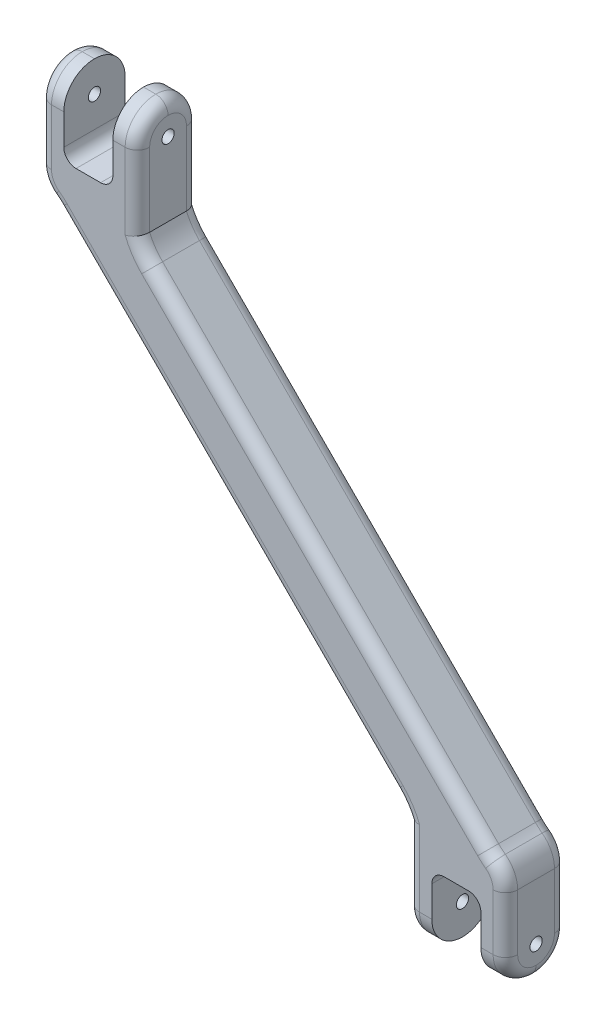
SolidWorks part; units mm, degrees
material "ABS"
ref_plane "Front Plane" through (0, 0, 0) normal (0, 0, 1) x (1, 0, 0)
ref_plane "Top Plane" through (0, 0, 0) normal (0, 1, 0) x (1, 0, 0)
ref_plane "Right Plane" through (0, 0, 0) normal (1, 0, 0) x (0, 0, -1)
sketch "Sketch1" plane through (0, 0, 0) normal (0, 0, 1) x (1, 0, 0)
  line L0 (-30, 30) -> (0, 0) construction
  line L1 (-38, 47) -> (-22, 47)
  line L2 (-38, 47) -> (-38, 30)
  line L3 (-38, 30) -> (-22, 30)
  line L4 (-22, 47) -> (-22, 30)
  line L5 (-34, 47) -> (-26, 47)
  line L6 (-34, 47) -> (-34, 35)
  line L7 (-34, 35) -> (-26, 35)
  line L8 (-26, 47) -> (-26, 35)
  line L9 (-37, 30) -> (-7, 0)
  line L10 (-7, 0) -> (7, 0)
  line L11 (7, 0) -> (-23, 30)
  line L12 (-37, 30) -> (-23, 30)
  line L13 (37, -30) -> (23, -30)
  line L14 (-7, 0) -> (23, -30)
  line L15 (7, 0) -> (-7, 0)
  line L16 (37, -30) -> (7, 0)
  line L17 (38, -47) -> (38, -30)
  line L18 (38, -47) -> (22, -47)
  line L19 (22, -47) -> (22, -30)
  line L20 (38, -30) -> (22, -30)
  line L21 (34, -47) -> (34, -35)
  line L22 (34, -47) -> (26, -47)
  line L23 (26, -47) -> (26, -35)
  line L24 (34, -35) -> (26, -35)
  point P8 (-34, 41)
  point P30 (0, 0)
  dimension "D1" = 8
  dimension "D2" = 4
  dimension "D3" = 4
  dimension "D4" = 12
  dimension "D5" = 5
  dimension "D6" = 45
  dimension "D7" = 14
  dimension "D8" = 7
  dimension "D9" = 30
  dimension "D10" = 7
  dimension "D12" = 30
  dimension "D13" = 30
  dimension "D11" = 2
extrude "Boss-Extrude1" add sketch "Sketch1" along normal blind 10 contours L1 L8 L7 L6 L2 L3 L12 L4 | L0 L3 L9 L10 | L12 L0 L15 L11 | L13 L16 L15 L10 L14 | L24 L21 L18 L17 L20 L13 L19 L23 region at (-11.5, 15, 0) region at (-18.5, 15, 0) region at (-33.5, 30.2335, 0) region at (15, -15, 0) region at (30, -30.2335, 0)
fillet "Fillet1" radius 10 4 edges at (23, -30, 5) (-23, 30, 5) (37, -30, 5) (-37, 30, 5)
fillet "Fillet2" radius 5 2 edges at (38, -30, 5) (-38, 30, 5)
fillet "Fillet3" radius 5 8 edges at (36, -47, 10) (36, -47, 0) (24, -47, 0) (24, -47, 10) (-36, 47, 0) (-36, 47, 10) (-24, 47, 0) (-24, 47, 10)
sketch "Sketch2" plane through (-22, 0, 0) normal (1, 0, 0) x (0, 0, -1)
  circle A0 centre (-5, 42) radius 1
  dimension "D1" = 2
extrude "Cut-Extrude1" cut sketch "Sketch2" against normal blind 16
sketch "Sketch3" plane through (38, 0, 0) normal (1, 0, 0) x (0, 0, -1)
  circle A0 centre (-5, -42) radius 1
  dimension "D1" = 2
extrude "Cut-Extrude2" cut sketch "Sketch3" against normal blind 16
fillet "Fillet4" radius 2 24 edges at (21.0917, -28.344, 0) (-35.4201, 28.3828, 0) (-37.4683, 30.604, 0) (-38, 37.4238, 0) (-38, 45.5355, 1.4645) (-38, 45.5355, 8.5355) (-38, 37.4238, 10) (-37.4683, 30.604, 10) (-35.4201, 28.3828, 10) (21.0917, -28.344, 10) (-21.0917, 28.344, 0) (35.4201, -28.3828, 0) (37.4683, -30.604, 0) (38, -37.4238, 0) (38, -45.5355, 1.4645) (38, -45.5355, 8.5355) (38, -37.4238, 10) (37.4683, -30.604, 10) (35.4201, -28.3828, 10) (-21.0917, 28.344, 10) (-7.5, 0.5, 0) (-7.5, 0.5, 10) (7.5, -0.5, 0) (7.5, -0.5, 10)
fillet "Fillet5" radius 2 8 edges at (22, -34.1171, 0) (22, -45.5355, 1.4645) (22, -45.5355, 8.5355) (-22, 34.1171, 0) (-22, 45.5355, 1.4645) (-22, 45.5355, 8.5355) (22, -34.1171, 10) (-22, 34.1171, 10)
fillet "Fillet6" radius 2 4 edges at (26, -35, 5) (34, -35, 5) (-26, 35, 5) (-34, 35, 5)
ref_axis "Axis1" through (-38, 42, 5) along (1, 0, 0)
ref_axis "Axis2" through (19.4744, -42, 5) along (1, 0, 0)
ref_plane "Plane1" through (-30, 0, 0) normal (-1, 0, 0) x (0, 0, 1)
ref_plane "Plane2" through (30, 0, 0) normal (-1, 0, 0) x (0, 0, 1)
ref_point "Point1"
ref_point "Point2"
ref_axis "Axis3" through (-30, 42, 5) along (0, -1, 0)
ref_axis "Axis4" through (30, -42, 5) along (0, 1, 0)
